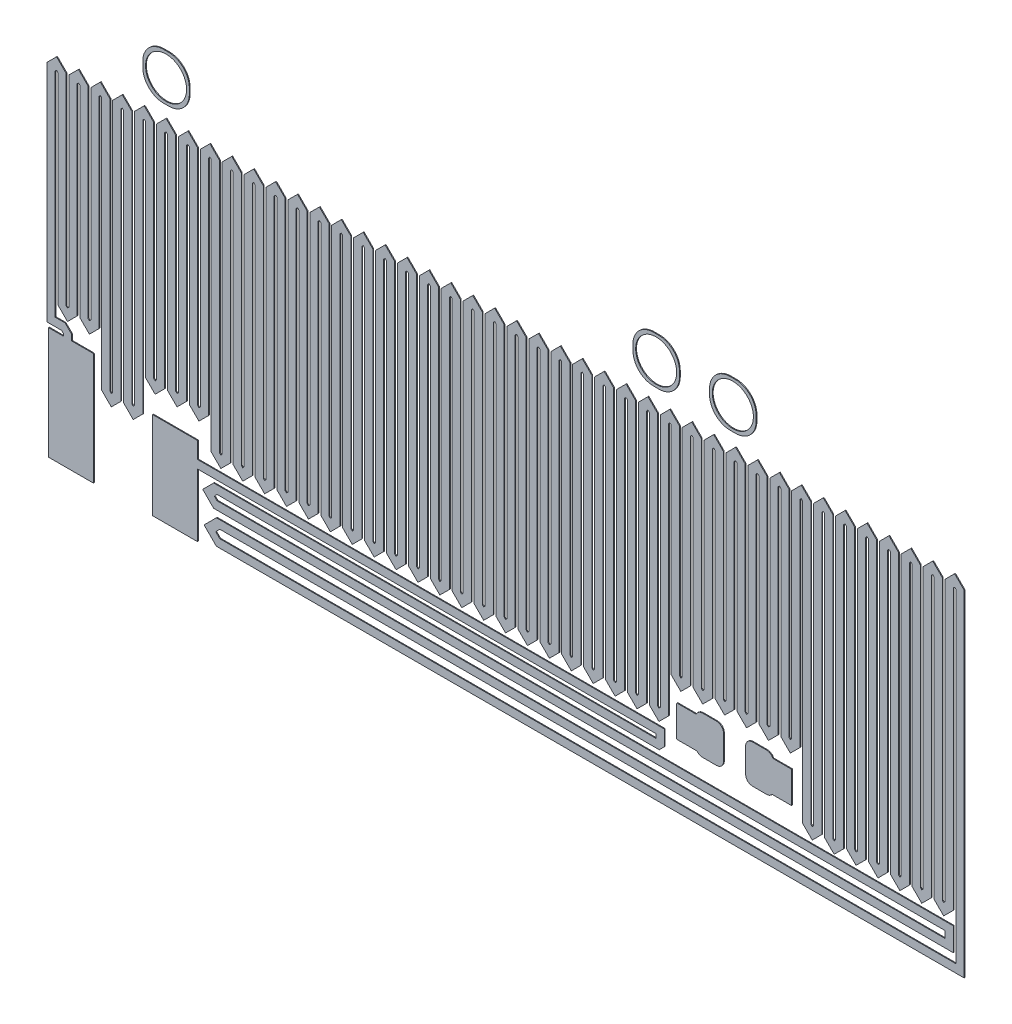
SolidWorks part; units mm, degrees
material "Pure Gold"
ref_plane "Front Plane" through (0, 0, 0) normal (0, 0, 1) x (1, 0, 0)
ref_plane "Top Plane" through (0, 0, 0) normal (0, 1, 0) x (1, 0, 0)
ref_plane "Right Plane" through (0, 0, 0) normal (1, 0, 0) x (0, 0, -1)
sketch "Sketch4" plane through (0, 0, 0) normal (0, 0, 1) x (1, 0, 0)
  line L0 (172.8, 114.607) -> (172.8, 114.657)
  line L1 (165.1587, 105.907) -> (165.211, 105.984)
  line L2 (165.211, 105.984) -> (165.292, 106.038)
  line L3 (165.292, 106.038) -> (165.387, 106.057)
  line L4 (165.387, 106.057) -> (165.912, 106.057)
  line L5 (165.912, 106.057) -> (166.008, 106.038)
  line L6 (166.008, 106.038) -> (166.089, 105.984)
  line L7 (166.089, 105.984) -> (166.143, 105.903)
  line L8 (166.143, 105.903) -> (166.162, 105.807)
  line L9 (166.162, 105.807) -> (166.162, 104.907)
  line L10 (166.162, 104.907) -> (166.143, 104.811)
  line L11 (166.143, 104.811) -> (166.089, 104.73)
  line L12 (166.089, 104.73) -> (166.008, 104.676)
  line L13 (166.008, 104.676) -> (165.912, 104.657)
  line L14 (165.912, 104.657) -> (165.387, 104.657)
  line L15 (165.387, 104.657) -> (165.292, 104.676)
  line L16 (165.292, 104.676) -> (165.211, 104.73)
  line L17 (165.211, 104.73) -> (165.1927, 104.757)
  line L18 (172, 114.607) -> (172, 114.657)
  line L19 (171.2, 114.607) -> (171.2, 114.657)
  line L20 (166.963, 105.807) -> (166.982, 105.903)
  line L21 (166.982, 105.903) -> (167.036, 105.984)
  line L22 (167.036, 105.984) -> (167.117, 106.038)
  line L23 (167.117, 106.038) -> (167.213, 106.057)
  line L24 (167.213, 106.057) -> (167.738, 106.057)
  line L25 (167.738, 106.057) -> (167.833, 106.038)
  line L26 (167.833, 106.038) -> (167.914, 105.984)
  line L27 (167.914, 105.984) -> (167.9663, 105.907)
  line L28 (170.4, 114.607) -> (170.4, 114.657)
  line L29 (169.6, 114.607) -> (169.6, 114.657)
  line L30 (168.8, 114.607) -> (168.8, 114.657)
  line L31 (167.9323, 104.757) -> (167.914, 104.73)
  line L32 (167.914, 104.73) -> (167.833, 104.676)
  line L33 (167.833, 104.676) -> (167.738, 104.657)
  line L34 (167.738, 104.657) -> (167.213, 104.657)
  line L35 (167.213, 104.657) -> (167.117, 104.676)
  line L36 (167.117, 104.676) -> (167.036, 104.73)
  line L37 (167.036, 104.73) -> (166.982, 104.811)
  line L38 (166.982, 104.811) -> (166.963, 104.907)
  line L39 (166.963, 104.907) -> (166.963, 105.807)
  line L40 (144.95, 115.507) -> (144.95, 117.207)
  line L41 (144.95, 117.207) -> (146.65, 117.207)
  line L42 (146.65, 117.207) -> (146.65, 115.507)
  line L43 (146.65, 115.507) -> (144.95, 115.507)
  line L44 (162.85, 115.507) -> (162.85, 117.207)
  line L45 (162.85, 117.207) -> (164.55, 117.207)
  line L46 (164.55, 117.207) -> (164.55, 115.507)
  line L47 (164.55, 115.507) -> (162.85, 115.507)
  line L48 (165.65, 115.507) -> (165.65, 117.207)
  line L49 (165.65, 117.207) -> (167.35, 117.207)
  line L50 (167.35, 117.207) -> (167.35, 115.507)
  line L51 (167.35, 115.507) -> (165.65, 115.507)
  line L52 (163.85, 104.357) -> (163.85, 104.707)
  line L53 (160.4, 114.657) -> (160.4, 105.407)
  line L54 (148.8, 114.657) -> (149, 114.857)
  line L55 (141.8, 114.807) -> (142, 114.607)
  line L56 (165.6, 106.757) -> (165.6, 114.607)
  line L57 (151.6, 114.657) -> (151.6, 105.407)
  line L58 (151.4, 114.857) -> (151.6, 114.657)
  line L59 (172, 104.457) -> (172, 114.607)
  line L60 (164, 104.857) -> (146.7, 104.857) construction
  line L61 (148.6, 105.207) -> (148.8, 105.407)
  line L62 (162.8, 114.657) -> (162.8, 105.407)
  line L63 (164, 105.407) -> (164, 114.607)
  line L64 (172.2, 114.857) -> (172.4, 114.657)
  line L65 (147.35, 104.007) -> (147.6, 104.257)
  line L66 (153.6, 105.407) -> (153.6, 114.607)
  line L67 (169.8, 114.857) -> (170, 114.657)
  line L68 (162, 105.407) -> (162.2, 105.207)
  line L69 (162.4, 114.657) -> (162.6, 114.857)
  line L70 (156.2, 114.857) -> (156.4, 114.657)
  line L71 (161, 114.857) -> (161.2, 114.657)
  line L72 (174.4, 114.657) -> (174.6, 114.857)
  line L73 (165.2, 114.657) -> (165.2, 106.757)
  line L74 (147.2, 114.657) -> (147.4, 114.857)
  line L75 (171.2, 104.457) -> (171.2, 114.607)
  line L76 (155.6, 114.657) -> (155.6, 105.407)
  line L77 (152, 105.407) -> (152, 114.607)
  line L78 (166, 106.807) -> (166.2, 106.607)
  line L79 (165.2, 106.757) -> (165.4, 106.557)
  line L80 (154, 105.407) -> (154.2, 105.207)
  line L81 (169.2, 104.457) -> (169.4, 104.257)
  line L82 (155, 105.207) -> (155.2, 105.407)
  line L83 (146, 114.657) -> (146, 106.557)
  line L84 (147.7, 103.207) -> (174.4, 103.207)
  line L85 (155.2, 114.657) -> (155.4, 114.857)
  line L86 (163.6, 114.657) -> (163.6, 105.407)
  line L87 (170.6, 114.857) -> (170.8, 114.657)
  line L88 (168.4, 106.807) -> (168.6, 106.607)
  line L89 (168.4, 114.657) -> (168.4, 106.807)
  line L90 (152, 114.657) -> (152.2, 114.857)
  line L91 (156, 105.407) -> (156, 114.607)
  line L92 (160.8, 114.657) -> (161, 114.857)
  line L93 (154.4, 114.657) -> (154.6, 114.857)
  line L94 (161.6, 114.657) -> (161.8, 114.857)
  line L95 (152.4, 114.657) -> (152.4, 105.407)
  line L96 (169.2, 114.657) -> (169.2, 104.457)
  line L97 (159.2, 114.657) -> (159.4, 114.857)
  line L98 (151.2, 114.657) -> (151.4, 114.857)
  line L99 (143.6, 114.607) -> (143.6, 105.357)
  line L100 (157.6, 114.657) -> (157.8, 114.857)
  line L101 (144, 114.607) -> (144.2, 114.807)
  line L102 (155.6, 105.407) -> (155.8, 105.207)
  line L103 (168.8, 106.807) -> (168.8, 114.607)
  line L104 (163, 105.207) -> (163.2, 105.407)
  line L105 (147, 106.307) -> (147.2, 106.507)
  line L106 (143.4, 114.807) -> (143.6, 114.607)
  line L107 (150.8, 114.657) -> (150.8, 105.407)
  line L108 (147.7, 102.607) -> (147.4, 102.907)
  line L109 (153.2, 105.407) -> (153.4, 105.207)
  line L110 (160.2, 114.857) -> (160.4, 114.657)
  line L111 (148.4, 105.407) -> (148.6, 105.207)
  line L112 (166.4, 106.807) -> (166.4, 114.607)
  line L113 (161.6, 105.407) -> (161.6, 114.607)
  line L114 (163.4, 114.857) -> (163.6, 114.657)
  line L115 (165, 114.857) -> (165.2, 114.657)
  line L116 (168, 114.657) -> (168.2, 114.857)
  line L117 (171.6, 114.657) -> (171.6, 104.457)
  line L118 (174.4, 103.757) -> (147.6, 103.757)
  line L119 (152.2, 114.857) -> (152.4, 114.657)
  line L120 (141.6, 114.607) -> (141.8, 114.807)
  line L121 (142, 114.607) -> (142, 107.257)
  line L122 (159.6, 114.657) -> (159.6, 105.407)
  line L123 (163.2, 114.657) -> (163.4, 114.857)
  line L124 (157.2, 105.407) -> (157.4, 105.207)
  line L125 (165.8, 114.857) -> (166, 114.657)
  line L126 (147.4, 102.907) -> (147.7, 103.207)
  line L127 (160.6, 105.207) -> (160.8, 105.407)
  line L128 (158.2, 105.207) -> (158.4, 105.407)
  line L129 (142.8, 107.257) -> (143, 107.057)
  line L130 (145.6, 114.657) -> (145.8, 114.857)
  line L131 (166.6, 114.857) -> (166.8, 114.657)
  line L132 (164.2, 114.857) -> (164.4, 114.657)
  line L133 (159.8, 105.207) -> (160, 105.407)
  line L134 (171.6, 104.457) -> (171.8, 104.257)
  line L135 (146.6, 114.857) -> (146.8, 114.657)
  line L136 (155.2, 105.407) -> (155.2, 114.607)
  line L137 (169.6, 114.657) -> (169.8, 114.857)
  line L138 (148.4, 114.657) -> (148.4, 105.407)
  line L139 (173, 114.857) -> (173.2, 114.657)
  line L140 (154.8, 105.407) -> (155, 105.207)
  line L141 (158.6, 114.857) -> (158.8, 114.657)
  line L142 (157.2, 114.657) -> (157.2, 105.407)
  line L143 (143.2, 114.607) -> (143.4, 114.807)
  line L144 (160, 105.407) -> (160, 114.607)
  line L145 (162.8, 105.407) -> (163, 105.207)
  line L146 (172, 114.657) -> (172.2, 114.857)
  line L147 (145.2, 106.557) -> (145.4, 106.357)
  line L148 (147.6, 104.257) -> (163.75, 104.257)
  line L149 (173.2, 114.657) -> (173.2, 104.457)
  line L150 (158.8, 114.657) -> (158.8, 105.407)
  line L151 (174, 104.457) -> (174.2, 104.257)
  line L152 (145, 114.857) -> (145.2, 114.657)
  line L153 (143.8, 105.157) -> (144, 105.357)
  line L154 (161.4, 105.207) -> (161.6, 105.407)
  line L155 (146, 106.557) -> (146.2, 106.357)
  line L156 (154.4, 105.407) -> (154.4, 114.607)
  line L157 (163.2, 105.407) -> (163.2, 114.607)
  line L158 (172.4, 114.657) -> (172.4, 104.457)
  line L159 (149, 114.857) -> (149.2, 114.657)
  line L160 (157.6, 105.407) -> (157.6, 114.607)
  line L161 (149.8, 114.857) -> (150, 114.657)
  line L162 (164.4, 106.757) -> (164.6, 106.557)
  line L163 (170, 114.657) -> (170, 104.407)
  line L164 (157, 114.857) -> (157.2, 114.657)
  line L165 (161.2, 105.407) -> (161.4, 105.207)
  line L166 (168.2, 114.857) -> (168.4, 114.657)
  line L167 (154.6, 114.857) -> (154.8, 114.657)
  line L168 (163.6, 105.407) -> (163.8, 105.207)
  line L169 (173.2, 104.457) -> (173.4, 104.257)
  line L170 (164.8, 106.757) -> (164.8, 114.607)
  line L171 (163.85, 104.707) -> (146.7, 104.707) construction
  line L172 (145.8, 114.857) -> (146, 114.657)
  line L173 (159.6, 105.407) -> (159.8, 105.207)
  line L174 (156.6, 105.207) -> (156.8, 105.407)
  line L175 (170.8, 114.657) -> (170.8, 104.457)
  line L176 (168.6, 106.607) -> (168.8, 106.807)
  line L177 (150.8, 105.407) -> (151, 105.207)
  line L178 (156.8, 105.407) -> (156.8, 114.607)
  line L179 (151.8, 105.207) -> (152, 105.407)
  line L180 (166, 114.657) -> (166, 106.807)
  line L181 (163.8, 105.207) -> (164, 105.407)
  line L182 (152.8, 105.407) -> (152.8, 114.607)
  line L183 (168.8, 114.657) -> (169, 114.857)
  line L184 (167.4, 114.857) -> (167.6, 114.657)
  line L185 (159.2, 105.407) -> (159.2, 114.607)
  line L186 (153, 114.857) -> (153.2, 114.657)
  line L187 (162.6, 114.857) -> (162.8, 114.657)
  line L188 (142.4, 114.607) -> (142.6, 114.807)
  line L189 (167.2, 106.807) -> (167.2, 114.607)
  line L190 (145.2, 114.657) -> (145.2, 106.557)
  line L191 (146.8, 114.657) -> (146.8, 106.507)
  line L192 (143.6, 105.357) -> (143.8, 105.157)
  line L193 (144.4, 105.357) -> (144.6, 105.157)
  line L194 (158, 114.657) -> (158, 105.407)
  line L195 (149.2, 105.407) -> (149.4, 105.207)
  line L196 (161.8, 114.857) -> (162, 114.657)
  line L197 (167.2, 114.657) -> (167.4, 114.857)
  line L198 (154.8, 114.657) -> (154.8, 105.407)
  line L199 (150, 114.657) -> (150, 105.407)
  line L200 (147.4, 114.857) -> (147.6, 114.657)
  line L201 (150.4, 105.407) -> (150.4, 114.607)
  line L202 (142.6, 114.807) -> (142.8, 114.607)
  line L203 (147.6, 105.407) -> (147.8, 105.207)
  line L204 (151, 105.207) -> (151.2, 105.407)
  line L205 (173.8, 114.857) -> (174, 114.657)
  line L206 (149.4, 105.207) -> (149.6, 105.407)
  line L207 (170, 104.407) -> (170.2, 104.207)
  line L208 (165.6, 114.657) -> (165.8, 114.857)
  line L209 (168, 106.807) -> (168, 114.607)
  line L210 (149.6, 114.657) -> (149.8, 114.857)
  line L211 (146.8, 106.507) -> (147, 106.307)
  line L212 (174.4, 104.457) -> (174.4, 114.657)
  line L213 (167.6, 106.807) -> (167.8, 106.607)
  line L214 (156.4, 105.407) -> (156.6, 105.207)
  line L215 (158.4, 105.407) -> (158.4, 114.607)
  line L216 (162.2, 105.207) -> (162.4, 105.407)
  line L217 (146.4, 106.557) -> (146.4, 114.607)
  line L218 (161.2, 114.657) -> (161.2, 105.407)
  line L219 (153.4, 105.207) -> (153.6, 105.407)
  line L220 (149.6, 105.407) -> (149.6, 114.607)
  line L221 (151.6, 105.407) -> (151.8, 105.207)
  line L222 (144.8, 105.407) -> (144.8, 114.607)
  line L223 (174.6, 114.857) -> (174.8, 114.657)
  line L224 (170.4, 104.407) -> (170.4, 114.607)
  line L225 (167.6, 114.657) -> (167.6, 106.807)
  line L226 (172.8, 114.657) -> (173, 114.857)
  line L227 (152.6, 105.207) -> (152.8, 105.407)
  line L228 (166.8, 114.657) -> (166.8, 106.807)
  line L229 (174.2, 104.257) -> (174.4, 104.457)
  line L230 (151.2, 105.407) -> (151.2, 114.607)
  line L231 (169.4, 104.257) -> (169.6, 104.457)
  line L232 (153.8, 114.857) -> (154, 114.657)
  line L233 (165.4, 106.557) -> (165.6, 106.757)
  line L234 (142.2, 107.057) -> (142.4, 107.257)
  line L235 (155.8, 105.207) -> (156, 105.407)
  line L236 (166.2, 106.607) -> (166.4, 106.807)
  line L237 (160.4, 105.407) -> (160.6, 105.207)
  line L238 (163.75, 104.257) -> (163.85, 104.357)
  line L239 (166.4, 114.657) -> (166.6, 114.857)
  line L240 (142.8, 114.607) -> (142.8, 107.257)
  line L241 (174.4, 103.207) -> (174.4, 103.757)
  line L242 (154.2, 105.207) -> (154.4, 105.407)
  line L243 (148.8, 105.407) -> (148.8, 114.607)
  line L244 (171.8, 104.257) -> (172, 104.457)
  line L245 (170.4, 114.657) -> (170.6, 114.857)
  line L246 (157.8, 114.857) -> (158, 114.657)
  line L247 (150.2, 105.207) -> (150.4, 105.407)
  line L248 (160, 114.657) -> (160.2, 114.857)
  line L249 (144, 105.357) -> (144, 114.557)
  line L250 (170.2, 104.207) -> (170.4, 104.407)
  line L251 (153.2, 114.657) -> (153.2, 105.407)
  line L252 (144.8, 114.657) -> (145, 114.857)
  line L253 (152.4, 105.407) -> (152.6, 105.207)
  line L254 (169, 114.857) -> (169.2, 114.657)
  line L255 (143, 107.057) -> (143.2, 107.257)
  line L256 (159, 105.207) -> (159.2, 105.407)
  line L257 (173.6, 114.657) -> (173.8, 114.857)
  line L258 (144.4, 114.607) -> (144.4, 105.357)
  line L259 (142.35, 106.307) -> (143.136, 106.307)
  line L260 (162, 114.657) -> (162, 105.407)
  line L261 (149.2, 114.657) -> (149.2, 105.407)
  line L262 (158, 105.407) -> (158.2, 105.207)
  line L263 (144.6, 105.157) -> (144.8, 105.357)
  line L264 (146.4, 114.657) -> (146.6, 114.857)
  line L265 (144.2, 114.807) -> (144.4, 114.607)
  line L266 (170.8, 104.457) -> (171, 104.257)
  line L267 (173.4, 104.257) -> (173.6, 104.457)
  line L268 (172.6, 104.257) -> (172.8, 104.457)
  line L269 (148.2, 114.857) -> (148.4, 114.657)
  line L270 (169.6, 104.457) -> (169.6, 114.607)
  line L271 (157.4, 105.207) -> (157.6, 105.407)
  line L272 (154, 114.657) -> (154, 105.407)
  line L273 (171, 104.257) -> (171.2, 104.457)
  line L274 (143.2, 107.257) -> (143.2, 114.557)
  line L275 (171.4, 114.857) -> (171.6, 114.657)
  line L276 (173.6, 104.457) -> (173.6, 114.657)
  line L277 (147.6, 103.757) -> (147.35, 104.007)
  line L278 (153.6, 114.657) -> (153.8, 114.857)
  line L279 (174.8, 102.607) -> (147.7, 102.607)
  line L280 (172.8, 104.457) -> (172.8, 114.607)
  line L281 (148, 105.407) -> (148, 114.607)
  line L282 (147.8, 105.207) -> (148, 105.407)
  line L283 (156, 114.657) -> (156.2, 114.857)
  line L284 (162.4, 105.407) -> (162.4, 114.607)
  line L285 (156.8, 114.657) -> (157, 114.857)
  line L286 (164.8, 114.657) -> (165, 114.857)
  line L287 (159.4, 114.857) -> (159.6, 114.657)
  line L288 (167, 106.607) -> (167.2, 106.807)
  line L289 (160.8, 105.407) -> (160.8, 114.607)
  line L290 (142.4, 107.257) -> (142.4, 114.557)
  line L291 (174, 114.657) -> (174, 104.457)
  line L292 (152.8, 114.657) -> (153, 114.857)
  line L293 (164, 114.657) -> (164.2, 114.857)
  line L294 (158.4, 114.657) -> (158.6, 114.857)
  line L295 (174.8, 114.657) -> (174.8, 102.607)
  line L296 (164.4, 114.657) -> (164.4, 106.757)
  line L297 (147.2, 106.507) -> (147.2, 114.607)
  line L298 (166.8, 106.807) -> (167, 106.607)
  line L299 (155.4, 114.857) -> (155.6, 114.657)
  line L300 (156.4, 114.657) -> (156.4, 105.407)
  line L301 (172.4, 104.457) -> (172.6, 104.257)
  line L302 (145.6, 106.557) -> (145.6, 114.607)
  line L303 (171.2, 114.657) -> (171.4, 114.857)
  line L304 (167.8, 106.607) -> (168, 106.807)
  line L305 (146.2, 106.357) -> (146.4, 106.557)
  line L306 (163.7, 104.557) -> (146.7, 104.557) construction
  line L307 (146.95, 104.557) -> (146.95, 102.271)
  line L308 (150.6, 114.857) -> (150.8, 114.657)
  line L309 (150, 105.407) -> (150.2, 105.207)
  line L310 (158.8, 105.407) -> (159, 105.207)
  line L311 (142, 107.257) -> (142.2, 107.057)
  line L312 (150.4, 114.657) -> (150.6, 114.857)
  line L313 (148, 114.657) -> (148.2, 114.857)
  line L314 (147.6, 114.657) -> (147.6, 105.407)
  line L315 (145.4, 106.357) -> (145.6, 106.557)
  line L316 (164.6, 106.557) -> (164.8, 106.757)
  line L317 (168, 114.607) -> (168, 114.657)
  line L318 (167.2, 114.607) -> (167.2, 114.657)
  line L319 (166.4, 114.607) -> (166.4, 114.657)
  line L320 (165.6, 114.607) -> (165.6, 114.657)
  line L321 (165.1927, 104.757) -> (164.464, 104.757)
  line L322 (164.464, 104.757) -> (164.454, 104.761)
  line L323 (164.454, 104.761) -> (164.45, 104.771)
  line L324 (164.45, 104.771) -> (164.45, 105.893)
  line L325 (164.45, 105.893) -> (164.454, 105.903)
  line L326 (164.454, 105.903) -> (164.464, 105.907)
  line L327 (164.464, 105.907) -> (165.1587, 105.907)
  line L328 (164.8, 114.607) -> (164.8, 114.657)
  line L329 (143.146, 106.303) -> (143.15, 106.293)
  line L330 (143.15, 106.293) -> (143.15, 102.222)
  line L331 (143.15, 102.222) -> (143.146, 102.212)
  line L332 (143.146, 102.212) -> (143.136, 102.208)
  line L333 (143.136, 102.208) -> (141.514, 102.208)
  line L334 (141.514, 102.208) -> (141.504, 102.212)
  line L335 (141.504, 102.212) -> (141.5, 102.222)
  line L336 (141.5, 102.222) -> (141.5, 106.293)
  line L337 (141.5, 106.293) -> (141.504, 106.303)
  line L338 (141.504, 106.303) -> (141.514, 106.307)
  line L339 (141.514, 106.307) -> (142.05, 106.307)
  line L340 (143.136, 106.307) -> (143.146, 106.303)
  line L341 (168.646, 105.903) -> (168.65, 105.893)
  line L342 (168.65, 105.893) -> (168.65, 104.771)
  line L343 (168.65, 104.771) -> (168.646, 104.761)
  line L344 (168.646, 104.761) -> (168.636, 104.757)
  line L345 (168.636, 104.757) -> (167.9323, 104.757)
  line L346 (164, 114.607) -> (164, 114.657)
  line L347 (163.2, 114.607) -> (163.2, 114.657)
  line L348 (162.4, 114.607) -> (162.4, 114.657)
  line L349 (161.6, 114.607) -> (161.6, 114.657)
  line L350 (160.8, 114.607) -> (160.8, 114.657)
  line L351 (167.9663, 105.907) -> (168.636, 105.907)
  line L352 (168.636, 105.907) -> (168.646, 105.903)
  line L353 (146.946, 105.453) -> (146.95, 105.443)
  line L354 (146.95, 105.443) -> (146.95, 104.857)
  line L355 (146.95, 102.271) -> (146.946, 102.261)
  line L356 (146.946, 102.261) -> (146.936, 102.257)
  line L357 (146.936, 102.257) -> (145.314, 102.257)
  line L358 (145.314, 102.257) -> (145.304, 102.261)
  line L359 (145.304, 102.261) -> (145.3, 102.271)
  line L360 (145.3, 102.271) -> (145.3, 105.443)
  line L361 (145.3, 105.443) -> (145.304, 105.453)
  line L362 (145.304, 105.453) -> (145.314, 105.457)
  line L363 (145.314, 105.457) -> (146.936, 105.457)
  line L364 (146.936, 105.457) -> (146.946, 105.453)
  line L365 (151.835, 117.707) -> (151.835, 115.608)
  line L366 (147.749, 115.608) -> (147.749, 117.707)
  line L367 (155.567, 115.608) -> (155.567, 117.707)
  line L368 (175.558, 102.207) -> (175.558, 117.707)
  line L369 (140.558, 117.707) -> (140.558, 102.207)
  line L370 (147.749, 117.707) -> (140.558, 117.707)
  line L371 (151.835, 115.608) -> (147.749, 115.608)
  line L372 (161.898, 117.707) -> (161.898, 115.608)
  line L373 (155.567, 117.707) -> (151.835, 117.707)
  line L374 (161.898, 115.608) -> (155.567, 115.608)
  line L375 (140.558, 102.207) -> (175.558, 102.207)
  line L376 (175.558, 117.707) -> (161.898, 117.707)
  line L377 (160, 114.607) -> (160, 114.657)
  line L378 (159.2, 114.607) -> (159.2, 114.657)
  line L379 (158.4, 114.607) -> (158.4, 114.657)
  line L380 (157.6, 114.607) -> (157.6, 114.657)
  line L381 (156.8, 114.607) -> (156.8, 114.657)
  line L382 (156, 114.607) -> (156, 114.657)
  line L383 (155.2, 114.607) -> (155.2, 114.657)
  line L384 (154.4, 114.607) -> (154.4, 114.657)
  line L385 (153.6, 114.607) -> (153.6, 114.657)
  line L386 (152.8, 114.607) -> (152.8, 114.657)
  line L387 (152, 114.607) -> (152, 114.657)
  line L388 (151.2, 114.607) -> (151.2, 114.657)
  line L389 (150.4, 114.607) -> (150.4, 114.657)
  line L390 (149.6, 114.607) -> (149.6, 114.657)
  line L391 (148.8, 114.607) -> (148.8, 114.657)
  line L392 (148, 114.607) -> (148, 114.657)
  line L393 (147.2, 114.607) -> (147.2, 114.657)
  line L394 (146.4, 114.607) -> (146.4, 114.657)
  line L395 (145.6, 114.607) -> (145.6, 114.657)
  line L396 (144.8, 114.607) -> (144.8, 114.657)
  line L397 (144, 114.557) -> (144, 114.607)
  line L398 (143.2, 114.557) -> (143.2, 114.607)
  line L399 (142.4, 114.557) -> (142.4, 114.607)
  line L400 (144.8, 105.357) -> (144.8, 105.407)
  line L401 (142.35, 106.307) -> (142.35, 106.5191)
  line L402 (142.35, 106.5191) -> (142.1121, 106.757)
  line L403 (142.1121, 106.757) -> (141.75, 106.757)
  line L404 (141.75, 106.757) -> (141.75, 114.5449)
  line L405 (141.75, 114.5449) -> (141.8, 114.5949)
  line L406 (141.8, 114.5949) -> (141.85, 114.5449)
  line L407 (141.85, 114.5449) -> (141.85, 107.1949)
  line L408 (141.85, 107.1949) -> (142.2, 106.8449)
  line L409 (142.2, 106.8449) -> (142.55, 107.1949)
  line L410 (142.55, 107.1949) -> (142.55, 114.5449)
  line L411 (142.55, 114.5449) -> (142.55, 114.5449)
  line L412 (142.55, 114.5449) -> (142.6, 114.5949)
  line L413 (142.6, 114.5949) -> (142.65, 114.5449)
  line L414 (142.65, 114.5449) -> (142.65, 107.1949)
  line L415 (142.65, 107.1949) -> (143, 106.8449)
  line L416 (143, 106.8449) -> (143.35, 107.1949)
  line L417 (143.35, 107.1949) -> (143.35, 114.5449)
  line L418 (143.35, 114.5449) -> (143.35, 114.5449)
  line L419 (143.35, 114.5449) -> (143.4, 114.5949)
  line L420 (143.4, 114.5949) -> (143.45, 114.5449)
  line L421 (143.45, 114.5449) -> (143.45, 105.2949)
  line L422 (143.45, 105.2949) -> (143.8, 104.9449)
  line L423 (143.8, 104.9449) -> (144.15, 105.2949)
  line L424 (144.15, 105.2949) -> (144.15, 114.5449)
  line L425 (144.15, 114.5449) -> (144.15, 114.5449)
  line L426 (144.15, 114.5449) -> (144.2, 114.5949)
  line L427 (144.2, 114.5949) -> (144.25, 114.5449)
  line L428 (144.25, 114.5449) -> (144.25, 105.2949)
  line L429 (144.25, 105.2949) -> (144.6, 104.9449)
  line L430 (144.6, 104.9449) -> (144.95, 105.2949)
  line L431 (144.95, 105.2949) -> (144.95, 105.407)
  line L432 (144.95, 105.407) -> (144.95, 114.5949)
  line L433 (144.95, 114.5949) -> (144.95, 114.5949)
  line L434 (144.95, 114.5949) -> (145, 114.6449)
  line L435 (145, 114.6449) -> (145.05, 114.5949)
  line L436 (145.05, 114.5949) -> (145.05, 106.4949)
  line L437 (145.05, 106.4949) -> (145.4, 106.1449)
  line L438 (145.4, 106.1449) -> (145.75, 106.4949)
  line L439 (145.75, 106.4949) -> (145.75, 114.5949)
  line L440 (145.75, 114.5949) -> (145.75, 114.5949)
  line L441 (145.75, 114.5949) -> (145.8, 114.6449)
  line L442 (145.8, 114.6449) -> (145.85, 114.5949)
  line L443 (145.85, 114.5949) -> (145.85, 106.4949)
  line L444 (145.85, 106.4949) -> (146.2, 106.1449)
  line L445 (146.2, 106.1449) -> (146.55, 106.4949)
  line L446 (146.55, 106.4949) -> (146.55, 114.5949)
  line L447 (146.55, 114.5949) -> (146.55, 114.5949)
  line L448 (146.55, 114.5949) -> (146.6, 114.6449)
  line L449 (146.6, 114.6449) -> (146.65, 114.5949)
  line L450 (146.65, 114.5949) -> (146.65, 106.4449)
  line L451 (146.65, 106.4449) -> (147, 106.0949)
  line L452 (147, 106.0949) -> (147.35, 106.4449)
  line L453 (147.35, 106.4449) -> (147.35, 114.5949)
  line L454 (147.35, 114.5949) -> (147.35, 114.5949)
  line L455 (147.35, 114.5949) -> (147.4, 114.6449)
  line L456 (147.4, 114.6449) -> (147.45, 114.5949)
  line L457 (147.45, 114.5949) -> (147.45, 105.3449)
  line L458 (147.45, 105.3449) -> (147.8, 104.9949)
  line L459 (147.8, 104.9949) -> (148.15, 105.3449)
  line L460 (148.15, 105.3449) -> (148.15, 114.5949)
  line L461 (148.15, 114.5949) -> (148.15, 114.5949)
  line L462 (148.15, 114.5949) -> (148.2, 114.6449)
  line L463 (148.2, 114.6449) -> (148.25, 114.5949)
  line L464 (148.25, 114.5949) -> (148.25, 105.3449)
  line L465 (148.25, 105.3449) -> (148.6, 104.9949)
  line L466 (148.6, 104.9949) -> (148.95, 105.3449)
  line L467 (148.95, 105.3449) -> (148.95, 114.5949)
  line L468 (148.95, 114.5949) -> (148.95, 114.5949)
  line L469 (148.95, 114.5949) -> (149, 114.6449)
  line L470 (149, 114.6449) -> (149.05, 114.5949)
  line L471 (149.05, 114.5949) -> (149.05, 105.3449)
  line L472 (149.05, 105.3449) -> (149.4, 104.9949)
  line L473 (149.4, 104.9949) -> (149.75, 105.3449)
  line L474 (149.75, 105.3449) -> (149.75, 114.5949)
  line L475 (149.75, 114.5949) -> (149.75, 114.5949)
  line L476 (149.75, 114.5949) -> (149.8, 114.6449)
  line L477 (149.8, 114.6449) -> (149.85, 114.5949)
  line L478 (149.85, 114.5949) -> (149.85, 105.3449)
  line L479 (149.85, 105.3449) -> (150.2, 104.9949)
  line L480 (150.2, 104.9949) -> (150.55, 105.3449)
  line L481 (150.55, 105.3449) -> (150.55, 114.5949)
  line L482 (150.55, 114.5949) -> (150.55, 114.5949)
  line L483 (150.55, 114.5949) -> (150.6, 114.6449)
  line L484 (150.6, 114.6449) -> (150.65, 114.5949)
  line L485 (150.65, 114.5949) -> (150.65, 105.3449)
  line L486 (150.65, 105.3449) -> (151, 104.9949)
  line L487 (151, 104.9949) -> (151.35, 105.3449)
  line L488 (151.35, 105.3449) -> (151.35, 114.5949)
  line L489 (151.35, 114.5949) -> (151.35, 114.5949)
  line L490 (151.35, 114.5949) -> (151.4, 114.6449)
  line L491 (151.4, 114.6449) -> (151.45, 114.5949)
  line L492 (151.45, 114.5949) -> (151.45, 105.3449)
  line L493 (151.45, 105.3449) -> (151.8, 104.9949)
  line L494 (151.8, 104.9949) -> (152.15, 105.3449)
  line L495 (152.15, 105.3449) -> (152.15, 114.5949)
  line L496 (152.15, 114.5949) -> (152.15, 114.5949)
  line L497 (152.15, 114.5949) -> (152.2, 114.6449)
  line L498 (152.2, 114.6449) -> (152.25, 114.5949)
  line L499 (152.25, 114.5949) -> (152.25, 105.3449)
  line L500 (152.25, 105.3449) -> (152.6, 104.9949)
  line L501 (152.6, 104.9949) -> (152.95, 105.3449)
  line L502 (152.95, 105.3449) -> (152.95, 114.5949)
  line L503 (152.95, 114.5949) -> (152.95, 114.5949)
  line L504 (152.95, 114.5949) -> (153, 114.6449)
  line L505 (153, 114.6449) -> (153.05, 114.5949)
  line L506 (153.05, 114.5949) -> (153.05, 105.3449)
  line L507 (153.05, 105.3449) -> (153.4, 104.9949)
  line L508 (153.4, 104.9949) -> (153.75, 105.3449)
  line L509 (153.75, 105.3449) -> (153.75, 114.5949)
  line L510 (153.75, 114.5949) -> (153.75, 114.5949)
  line L511 (153.75, 114.5949) -> (153.8, 114.6449)
  line L512 (153.8, 114.6449) -> (153.85, 114.5949)
  line L513 (153.85, 114.5949) -> (153.85, 105.3449)
  line L514 (153.85, 105.3449) -> (154.2, 104.9949)
  line L515 (154.2, 104.9949) -> (154.55, 105.3449)
  line L516 (154.55, 105.3449) -> (154.55, 114.5949)
  line L517 (154.55, 114.5949) -> (154.55, 114.5949)
  line L518 (154.55, 114.5949) -> (154.6, 114.6449)
  line L519 (154.6, 114.6449) -> (154.65, 114.5949)
  line L520 (154.65, 114.5949) -> (154.65, 105.3449)
  line L521 (154.65, 105.3449) -> (155, 104.9949)
  line L522 (155, 104.9949) -> (155.35, 105.3449)
  line L523 (155.35, 105.3449) -> (155.35, 114.5949)
  line L524 (155.35, 114.5949) -> (155.35, 114.5949)
  line L525 (155.35, 114.5949) -> (155.4, 114.6449)
  line L526 (155.4, 114.6449) -> (155.45, 114.5949)
  line L527 (155.45, 114.5949) -> (155.45, 105.3449)
  line L528 (155.45, 105.3449) -> (155.8, 104.9949)
  line L529 (155.8, 104.9949) -> (156.15, 105.3449)
  line L530 (156.15, 105.3449) -> (156.15, 114.5949)
  line L531 (156.15, 114.5949) -> (156.15, 114.5949)
  line L532 (156.15, 114.5949) -> (156.2, 114.6449)
  line L533 (156.2, 114.6449) -> (156.25, 114.5949)
  line L534 (156.25, 114.5949) -> (156.25, 105.3449)
  line L535 (156.25, 105.3449) -> (156.6, 104.9949)
  line L536 (156.6, 104.9949) -> (156.95, 105.3449)
  line L537 (156.95, 105.3449) -> (156.95, 114.5949)
  line L538 (156.95, 114.5949) -> (156.95, 114.5949)
  line L539 (156.95, 114.5949) -> (157, 114.6449)
  line L540 (157, 114.6449) -> (157.05, 114.5949)
  line L541 (157.05, 114.5949) -> (157.05, 105.3449)
  line L542 (157.05, 105.3449) -> (157.4, 104.9949)
  line L543 (157.4, 104.9949) -> (157.75, 105.3449)
  line L544 (157.75, 105.3449) -> (157.75, 114.5949)
  line L545 (157.75, 114.5949) -> (157.75, 114.5949)
  line L546 (157.75, 114.5949) -> (157.8, 114.6449)
  line L547 (157.8, 114.6449) -> (157.85, 114.5949)
  line L548 (157.85, 114.5949) -> (157.85, 105.3449)
  line L549 (157.85, 105.3449) -> (158.2, 104.9949)
  line L550 (158.2, 104.9949) -> (158.55, 105.3449)
  line L551 (158.55, 105.3449) -> (158.55, 114.5949)
  line L552 (158.55, 114.5949) -> (158.55, 114.5949)
  line L553 (158.55, 114.5949) -> (158.6, 114.6449)
  line L554 (158.6, 114.6449) -> (158.65, 114.5949)
  line L555 (158.65, 114.5949) -> (158.65, 105.3449)
  line L556 (158.65, 105.3449) -> (159, 104.9949)
  line L557 (159, 104.9949) -> (159.35, 105.3449)
  line L558 (159.35, 105.3449) -> (159.35, 114.5949)
  line L559 (159.35, 114.5949) -> (159.35, 114.5949)
  line L560 (159.35, 114.5949) -> (159.4, 114.6449)
  line L561 (159.4, 114.6449) -> (159.45, 114.5949)
  line L562 (159.45, 114.5949) -> (159.45, 105.3449)
  line L563 (159.45, 105.3449) -> (159.8, 104.9949)
  line L564 (159.8, 104.9949) -> (160.15, 105.3449)
  line L565 (160.15, 105.3449) -> (160.15, 114.5949)
  line L566 (160.15, 114.5949) -> (160.15, 114.5949)
  line L567 (160.15, 114.5949) -> (160.2, 114.6449)
  line L568 (160.2, 114.6449) -> (160.25, 114.5949)
  line L569 (160.25, 114.5949) -> (160.25, 105.3449)
  line L570 (160.25, 105.3449) -> (160.6, 104.9949)
  line L571 (160.6, 104.9949) -> (160.95, 105.3449)
  line L572 (160.95, 105.3449) -> (160.95, 114.5949)
  line L573 (160.95, 114.5949) -> (160.95, 114.5949)
  line L574 (160.95, 114.5949) -> (161, 114.6449)
  line L575 (161, 114.6449) -> (161.05, 114.5949)
  line L576 (161.05, 114.5949) -> (161.05, 105.3449)
  line L577 (161.05, 105.3449) -> (161.4, 104.9949)
  line L578 (161.4, 104.9949) -> (161.75, 105.3449)
  line L579 (161.75, 105.3449) -> (161.75, 114.5949)
  line L580 (161.75, 114.5949) -> (161.75, 114.5949)
  line L581 (161.75, 114.5949) -> (161.8, 114.6449)
  line L582 (161.8, 114.6449) -> (161.85, 114.5949)
  line L583 (161.85, 114.5949) -> (161.85, 105.3449)
  line L584 (161.85, 105.3449) -> (162.2, 104.9949)
  line L585 (162.2, 104.9949) -> (162.55, 105.3449)
  line L586 (162.55, 105.3449) -> (162.55, 114.5949)
  line L587 (162.55, 114.5949) -> (162.55, 114.5949)
  line L588 (162.55, 114.5949) -> (162.6, 114.6449)
  line L589 (162.6, 114.6449) -> (162.65, 114.5949)
  line L590 (162.65, 114.5949) -> (162.65, 105.3449)
  line L591 (162.65, 105.3449) -> (163, 104.9949)
  line L592 (163, 104.9949) -> (163.35, 105.3449)
  line L593 (163.35, 105.3449) -> (163.35, 114.5949)
  line L594 (163.35, 114.5949) -> (163.35, 114.5949)
  line L595 (163.35, 114.5949) -> (163.4, 114.6449)
  line L596 (163.4, 114.6449) -> (163.45, 114.5949)
  line L597 (163.45, 114.5949) -> (163.45, 105.3449)
  line L598 (163.45, 105.3449) -> (163.8, 104.9949)
  line L599 (163.8, 104.9949) -> (164.15, 105.3449)
  line L600 (164.15, 105.3449) -> (164.15, 114.5949)
  line L601 (164.15, 114.5949) -> (164.15, 114.5949)
  line L602 (164.15, 114.5949) -> (164.2, 114.6449)
  line L603 (164.2, 114.6449) -> (164.25, 114.5949)
  line L604 (164.25, 114.5949) -> (164.25, 106.6949)
  line L605 (164.25, 106.6949) -> (164.6, 106.3449)
  line L606 (164.6, 106.3449) -> (164.95, 106.6949)
  line L607 (164.95, 106.6949) -> (164.95, 114.5949)
  line L608 (164.95, 114.5949) -> (164.95, 114.5949)
  line L609 (164.95, 114.5949) -> (165, 114.6449)
  line L610 (165, 114.6449) -> (165.05, 114.5949)
  line L611 (165.05, 114.5949) -> (165.05, 106.6949)
  line L612 (165.05, 106.6949) -> (165.4, 106.3449)
  line L613 (165.4, 106.3449) -> (165.75, 106.6949)
  line L614 (165.75, 106.6949) -> (165.75, 114.5949)
  line L615 (165.75, 114.5949) -> (165.75, 114.5949)
  line L616 (165.75, 114.5949) -> (165.8, 114.6449)
  line L617 (165.8, 114.6449) -> (165.85, 114.5949)
  line L618 (165.85, 114.5949) -> (165.85, 106.7449)
  line L619 (165.85, 106.7449) -> (166.2, 106.3949)
  line L620 (166.2, 106.3949) -> (166.55, 106.7449)
  line L621 (166.55, 106.7449) -> (166.55, 114.5949)
  line L622 (166.55, 114.5949) -> (166.55, 114.5949)
  line L623 (166.55, 114.5949) -> (166.6, 114.6449)
  line L624 (166.6, 114.6449) -> (166.65, 114.5949)
  line L625 (166.65, 114.5949) -> (166.65, 106.7449)
  line L626 (166.65, 106.7449) -> (167, 106.3949)
  line L627 (167, 106.3949) -> (167.35, 106.7449)
  line L628 (167.35, 106.7449) -> (167.35, 114.5949)
  line L629 (167.35, 114.5949) -> (167.35, 114.5949)
  line L630 (167.35, 114.5949) -> (167.4, 114.6449)
  line L631 (167.4, 114.6449) -> (167.45, 114.5949)
  line L632 (167.45, 114.5949) -> (167.45, 106.7449)
  line L633 (167.45, 106.7449) -> (167.8, 106.3949)
  line L634 (167.8, 106.3949) -> (168.15, 106.7449)
  line L635 (168.15, 106.7449) -> (168.15, 114.5949)
  line L636 (168.15, 114.5949) -> (168.15, 114.5949)
  line L637 (168.15, 114.5949) -> (168.2, 114.6449)
  line L638 (168.2, 114.6449) -> (168.25, 114.5949)
  line L639 (168.25, 114.5949) -> (168.25, 106.7449)
  line L640 (168.25, 106.7449) -> (168.6, 106.3949)
  line L641 (168.6, 106.3949) -> (168.95, 106.7449)
  line L642 (168.95, 106.7449) -> (168.95, 114.5949)
  line L643 (168.95, 114.5949) -> (168.95, 114.5949)
  line L644 (168.95, 114.5949) -> (169, 114.6449)
  line L645 (169, 114.6449) -> (169.05, 114.5949)
  line L646 (169.05, 114.5949) -> (169.05, 104.3949)
  line L647 (169.05, 104.3949) -> (169.4, 104.0449)
  line L648 (169.4, 104.0449) -> (169.75, 104.3949)
  line L649 (169.75, 104.3949) -> (169.75, 114.5949)
  line L650 (169.75, 114.5949) -> (169.75, 114.5949)
  line L651 (169.75, 114.5949) -> (169.8, 114.6449)
  line L652 (169.8, 114.6449) -> (169.85, 114.5949)
  line L653 (169.85, 114.5949) -> (169.85, 104.3449)
  line L654 (169.85, 104.3449) -> (170.2, 103.9949)
  line L655 (170.2, 103.9949) -> (170.55, 104.3449)
  line L656 (170.55, 104.3449) -> (170.55, 114.5949)
  line L657 (170.55, 114.5949) -> (170.55, 114.5949)
  line L658 (170.55, 114.5949) -> (170.6, 114.6449)
  line L659 (170.6, 114.6449) -> (170.65, 114.5949)
  line L660 (170.65, 114.5949) -> (170.65, 104.3949)
  line L661 (170.65, 104.3949) -> (171, 104.0449)
  line L662 (171, 104.0449) -> (171.35, 104.3949)
  line L663 (171.35, 104.3949) -> (171.35, 114.5949)
  line L664 (171.35, 114.5949) -> (171.35, 114.5949)
  line L665 (171.35, 114.5949) -> (171.4, 114.6449)
  line L666 (171.4, 114.6449) -> (171.45, 114.5949)
  line L667 (171.45, 114.5949) -> (171.45, 104.3949)
  line L668 (171.45, 104.3949) -> (171.8, 104.0449)
  line L669 (171.8, 104.0449) -> (172.15, 104.3949)
  line L670 (172.15, 104.3949) -> (172.15, 114.5949)
  line L671 (172.15, 114.5949) -> (172.15, 114.5949)
  line L672 (172.15, 114.5949) -> (172.2, 114.6449)
  line L673 (172.2, 114.6449) -> (172.25, 114.5949)
  line L674 (172.25, 114.5949) -> (172.25, 104.3949)
  line L675 (172.25, 104.3949) -> (172.6, 104.0449)
  line L676 (172.6, 104.0449) -> (172.95, 104.3949)
  line L677 (172.95, 104.3949) -> (172.95, 114.5949)
  line L678 (172.95, 114.5949) -> (172.95, 114.5949)
  line L679 (172.95, 114.5949) -> (173, 114.6449)
  line L680 (173, 114.6449) -> (173.05, 114.5949)
  line L681 (173.05, 114.5949) -> (173.05, 104.3949)
  line L682 (173.05, 104.3949) -> (173.4, 104.0449)
  line L683 (173.4, 104.0449) -> (173.75, 104.3949)
  line L684 (173.75, 104.3949) -> (173.75, 114.5949)
  line L685 (173.75, 114.5949) -> (173.8, 114.6449)
  line L686 (173.8, 114.6449) -> (173.85, 114.5949)
  line L687 (173.85, 114.5949) -> (173.85, 104.3949)
  line L688 (173.85, 104.3949) -> (174.2, 104.0449)
  line L689 (174.2, 104.0449) -> (174.55, 104.3949)
  line L690 (174.55, 104.3949) -> (174.55, 114.5949)
  line L691 (174.55, 114.5949) -> (174.6, 114.6449)
  line L692 (174.6, 114.6449) -> (174.65, 114.5949)
  line L693 (174.65, 114.5949) -> (174.65, 102.757)
  line L694 (174.65, 102.757) -> (147.7621, 102.757)
  line L695 (147.7621, 102.757) -> (147.6121, 102.907)
  line L696 (147.6121, 102.907) -> (147.7621, 103.057)
  line L697 (147.7621, 103.057) -> (174.55, 103.057)
  line L698 (174.55, 103.057) -> (174.55, 103.907)
  line L699 (174.55, 103.907) -> (147.6621, 103.907)
  line L700 (147.6621, 103.907) -> (147.5621, 104.007)
  line L701 (147.5621, 104.007) -> (147.6621, 104.107)
  line L702 (147.6621, 104.107) -> (163.8121, 104.107)
  line L703 (163.8121, 104.107) -> (164, 104.2949)
  line L704 (164, 104.2949) -> (164, 104.857)
  line L705 (164, 104.857) -> (146.95, 104.857)
  line L706 (142.05, 106.307) -> (142.05, 106.3949)
  line L707 (142.05, 106.3949) -> (141.9879, 106.457)
  line L708 (141.9879, 106.457) -> (141.45, 106.457)
  line L709 (141.45, 106.457) -> (141.45, 114.6691)
  line L710 (141.45, 114.6691) -> (141.8, 115.0191)
  line L711 (141.8, 115.0191) -> (142.15, 114.6691)
  line L712 (142.15, 114.6691) -> (142.15, 107.3191)
  line L713 (142.15, 107.3191) -> (142.2, 107.2691)
  line L714 (142.2, 107.2691) -> (142.25, 107.3191)
  line L715 (142.25, 107.3191) -> (142.25, 114.557)
  line L716 (142.25, 114.557) -> (142.25, 114.6691)
  line L717 (142.25, 114.6691) -> (142.6, 115.0191)
  line L718 (142.6, 115.0191) -> (142.95, 114.6691)
  line L719 (142.95, 114.6691) -> (142.95, 107.3191)
  line L720 (142.95, 107.3191) -> (143, 107.2691)
  line L721 (143, 107.2691) -> (143.05, 107.3191)
  line L722 (143.05, 107.3191) -> (143.05, 114.557)
  line L723 (143.05, 114.557) -> (143.05, 114.6691)
  line L724 (143.05, 114.6691) -> (143.4, 115.0191)
  line L725 (143.4, 115.0191) -> (143.75, 114.6691)
  line L726 (143.75, 114.6691) -> (143.75, 105.4191)
  line L727 (143.75, 105.4191) -> (143.8, 105.3691)
  line L728 (143.8, 105.3691) -> (143.85, 105.4191)
  line L729 (143.85, 105.4191) -> (143.85, 114.557)
  line L730 (143.85, 114.557) -> (143.85, 114.6691)
  line L731 (143.85, 114.6691) -> (144.2, 115.0191)
  line L732 (144.2, 115.0191) -> (144.55, 114.6691)
  line L733 (144.55, 114.6691) -> (144.55, 105.4191)
  line L734 (144.55, 105.4191) -> (144.6, 105.3691)
  line L735 (144.6, 105.3691) -> (144.65, 105.4191)
  line L736 (144.65, 105.4191) -> (144.65, 105.4191)
  line L737 (144.65, 105.4191) -> (144.65, 114.607)
  line L738 (144.65, 114.607) -> (144.65, 114.7191)
  line L739 (144.65, 114.7191) -> (145, 115.0691)
  line L740 (145, 115.0691) -> (145.35, 114.7191)
  line L741 (145.35, 114.7191) -> (145.35, 106.6191)
  line L742 (145.35, 106.6191) -> (145.4, 106.5691)
  line L743 (145.4, 106.5691) -> (145.45, 106.6191)
  line L744 (145.45, 106.6191) -> (145.45, 114.607)
  line L745 (145.45, 114.607) -> (145.45, 114.7191)
  line L746 (145.45, 114.7191) -> (145.8, 115.0691)
  line L747 (145.8, 115.0691) -> (146.15, 114.7191)
  line L748 (146.15, 114.7191) -> (146.15, 106.6191)
  line L749 (146.15, 106.6191) -> (146.2, 106.5691)
  line L750 (146.2, 106.5691) -> (146.25, 106.6191)
  line L751 (146.25, 106.6191) -> (146.25, 114.607)
  line L752 (146.25, 114.607) -> (146.25, 114.7191)
  line L753 (146.25, 114.7191) -> (146.6, 115.0691)
  line L754 (146.6, 115.0691) -> (146.95, 114.7191)
  line L755 (146.95, 114.7191) -> (146.95, 106.5691)
  line L756 (146.95, 106.5691) -> (147, 106.5191)
  line L757 (147, 106.5191) -> (147.05, 106.5691)
  line L758 (147.05, 106.5691) -> (147.05, 114.607)
  line L759 (147.05, 114.607) -> (147.05, 114.7191)
  line L760 (147.05, 114.7191) -> (147.4, 115.0691)
  line L761 (147.4, 115.0691) -> (147.75, 114.7191)
  line L762 (147.75, 114.7191) -> (147.75, 105.4691)
  line L763 (147.75, 105.4691) -> (147.8, 105.4191)
  line L764 (147.8, 105.4191) -> (147.85, 105.4691)
  line L765 (147.85, 105.4691) -> (147.85, 114.607)
  line L766 (147.85, 114.607) -> (147.85, 114.7191)
  line L767 (147.85, 114.7191) -> (148.2, 115.0691)
  line L768 (148.2, 115.0691) -> (148.55, 114.7191)
  line L769 (148.55, 114.7191) -> (148.55, 105.4691)
  line L770 (148.55, 105.4691) -> (148.6, 105.4191)
  line L771 (148.6, 105.4191) -> (148.65, 105.4691)
  line L772 (148.65, 105.4691) -> (148.65, 114.607)
  line L773 (148.65, 114.607) -> (148.65, 114.7191)
  line L774 (148.65, 114.7191) -> (149, 115.0691)
  line L775 (149, 115.0691) -> (149.35, 114.7191)
  line L776 (149.35, 114.7191) -> (149.35, 105.4691)
  line L777 (149.35, 105.4691) -> (149.4, 105.4191)
  line L778 (149.4, 105.4191) -> (149.45, 105.4691)
  line L779 (149.45, 105.4691) -> (149.45, 114.607)
  line L780 (149.45, 114.607) -> (149.45, 114.7191)
  line L781 (149.45, 114.7191) -> (149.8, 115.0691)
  line L782 (149.8, 115.0691) -> (150.15, 114.7191)
  line L783 (150.15, 114.7191) -> (150.15, 105.4691)
  line L784 (150.15, 105.4691) -> (150.2, 105.4191)
  line L785 (150.2, 105.4191) -> (150.25, 105.4691)
  line L786 (150.25, 105.4691) -> (150.25, 114.607)
  line L787 (150.25, 114.607) -> (150.25, 114.7191)
  line L788 (150.25, 114.7191) -> (150.6, 115.0691)
  line L789 (150.6, 115.0691) -> (150.95, 114.7191)
  line L790 (150.95, 114.7191) -> (150.95, 105.4691)
  line L791 (150.95, 105.4691) -> (151, 105.4191)
  line L792 (151, 105.4191) -> (151.05, 105.4691)
  line L793 (151.05, 105.4691) -> (151.05, 114.607)
  line L794 (151.05, 114.607) -> (151.05, 114.7191)
  line L795 (151.05, 114.7191) -> (151.4, 115.0691)
  line L796 (151.4, 115.0691) -> (151.75, 114.7191)
  line L797 (151.75, 114.7191) -> (151.75, 105.4691)
  line L798 (151.75, 105.4691) -> (151.8, 105.4191)
  line L799 (151.8, 105.4191) -> (151.85, 105.4691)
  line L800 (151.85, 105.4691) -> (151.85, 114.607)
  line L801 (151.85, 114.607) -> (151.85, 114.7191)
  line L802 (151.85, 114.7191) -> (152.2, 115.0691)
  line L803 (152.2, 115.0691) -> (152.55, 114.7191)
  line L804 (152.55, 114.7191) -> (152.55, 105.4691)
  line L805 (152.55, 105.4691) -> (152.6, 105.4191)
  line L806 (152.6, 105.4191) -> (152.65, 105.4691)
  line L807 (152.65, 105.4691) -> (152.65, 114.607)
  line L808 (152.65, 114.607) -> (152.65, 114.7191)
  line L809 (152.65, 114.7191) -> (153, 115.0691)
  line L810 (153, 115.0691) -> (153.35, 114.7191)
  line L811 (153.35, 114.7191) -> (153.35, 105.4691)
  line L812 (153.35, 105.4691) -> (153.4, 105.4191)
  line L813 (153.4, 105.4191) -> (153.45, 105.4691)
  line L814 (153.45, 105.4691) -> (153.45, 114.607)
  line L815 (153.45, 114.607) -> (153.45, 114.7191)
  line L816 (153.45, 114.7191) -> (153.8, 115.0691)
  line L817 (153.8, 115.0691) -> (154.15, 114.7191)
  line L818 (154.15, 114.7191) -> (154.15, 105.4691)
  line L819 (154.15, 105.4691) -> (154.2, 105.4191)
  line L820 (154.2, 105.4191) -> (154.25, 105.4691)
  line L821 (154.25, 105.4691) -> (154.25, 114.607)
  line L822 (154.25, 114.607) -> (154.25, 114.7191)
  line L823 (154.25, 114.7191) -> (154.6, 115.0691)
  line L824 (154.6, 115.0691) -> (154.95, 114.7191)
  line L825 (154.95, 114.7191) -> (154.95, 105.4691)
  line L826 (154.95, 105.4691) -> (155, 105.4191)
  line L827 (155, 105.4191) -> (155.05, 105.4691)
  line L828 (155.05, 105.4691) -> (155.05, 114.607)
  line L829 (155.05, 114.607) -> (155.05, 114.7191)
  line L830 (155.05, 114.7191) -> (155.4, 115.0691)
  line L831 (155.4, 115.0691) -> (155.75, 114.7191)
  line L832 (155.75, 114.7191) -> (155.75, 105.4691)
  line L833 (155.75, 105.4691) -> (155.8, 105.4191)
  line L834 (155.8, 105.4191) -> (155.85, 105.4691)
  line L835 (155.85, 105.4691) -> (155.85, 114.607)
  line L836 (155.85, 114.607) -> (155.85, 114.7191)
  line L837 (155.85, 114.7191) -> (156.2, 115.0691)
  line L838 (156.2, 115.0691) -> (156.55, 114.7191)
  line L839 (156.55, 114.7191) -> (156.55, 105.4691)
  line L840 (156.55, 105.4691) -> (156.6, 105.4191)
  line L841 (156.6, 105.4191) -> (156.65, 105.4691)
  line L842 (156.65, 105.4691) -> (156.65, 114.607)
  line L843 (156.65, 114.607) -> (156.65, 114.7191)
  line L844 (156.65, 114.7191) -> (157, 115.0691)
  line L845 (157, 115.0691) -> (157.35, 114.7191)
  line L846 (157.35, 114.7191) -> (157.35, 105.4691)
  line L847 (157.35, 105.4691) -> (157.4, 105.4191)
  line L848 (157.4, 105.4191) -> (157.45, 105.4691)
  line L849 (157.45, 105.4691) -> (157.45, 114.607)
  line L850 (157.45, 114.607) -> (157.45, 114.7191)
  line L851 (157.45, 114.7191) -> (157.8, 115.0691)
  line L852 (157.8, 115.0691) -> (158.15, 114.7191)
  line L853 (158.15, 114.7191) -> (158.15, 105.4691)
  line L854 (158.15, 105.4691) -> (158.2, 105.4191)
  line L855 (158.2, 105.4191) -> (158.25, 105.4691)
  line L856 (158.25, 105.4691) -> (158.25, 114.607)
  line L857 (158.25, 114.607) -> (158.25, 114.7191)
  line L858 (158.25, 114.7191) -> (158.6, 115.0691)
  line L859 (158.6, 115.0691) -> (158.95, 114.7191)
  line L860 (158.95, 114.7191) -> (158.95, 105.4691)
  line L861 (158.95, 105.4691) -> (159, 105.4191)
  line L862 (159, 105.4191) -> (159.05, 105.4691)
  line L863 (159.05, 105.4691) -> (159.05, 114.607)
  line L864 (159.05, 114.607) -> (159.05, 114.7191)
  line L865 (159.05, 114.7191) -> (159.4, 115.0691)
  line L866 (159.4, 115.0691) -> (159.75, 114.7191)
  line L867 (159.75, 114.7191) -> (159.75, 105.4691)
  line L868 (159.75, 105.4691) -> (159.8, 105.4191)
  line L869 (159.8, 105.4191) -> (159.85, 105.4691)
  line L870 (159.85, 105.4691) -> (159.85, 114.607)
  line L871 (159.85, 114.607) -> (159.85, 114.7191)
  line L872 (159.85, 114.7191) -> (160.2, 115.0691)
  line L873 (160.2, 115.0691) -> (160.55, 114.7191)
  line L874 (160.55, 114.7191) -> (160.55, 105.4691)
  line L875 (160.55, 105.4691) -> (160.6, 105.4191)
  line L876 (160.6, 105.4191) -> (160.65, 105.4691)
  line L877 (160.65, 105.4691) -> (160.65, 114.607)
  line L878 (160.65, 114.607) -> (160.65, 114.7191)
  line L879 (160.65, 114.7191) -> (161, 115.0691)
  line L880 (161, 115.0691) -> (161.35, 114.7191)
  line L881 (161.35, 114.7191) -> (161.35, 105.4691)
  line L882 (161.35, 105.4691) -> (161.4, 105.4191)
  line L883 (161.4, 105.4191) -> (161.45, 105.4691)
  line L884 (161.45, 105.4691) -> (161.45, 114.607)
  line L885 (161.45, 114.607) -> (161.45, 114.7191)
  line L886 (161.45, 114.7191) -> (161.8, 115.0691)
  line L887 (161.8, 115.0691) -> (162.15, 114.7191)
  line L888 (162.15, 114.7191) -> (162.15, 105.4691)
  line L889 (162.15, 105.4691) -> (162.2, 105.4191)
  line L890 (162.2, 105.4191) -> (162.25, 105.4691)
  line L891 (162.25, 105.4691) -> (162.25, 114.607)
  line L892 (162.25, 114.607) -> (162.25, 114.7191)
  line L893 (162.25, 114.7191) -> (162.6, 115.0691)
  line L894 (162.6, 115.0691) -> (162.95, 114.7191)
  line L895 (162.95, 114.7191) -> (162.95, 105.4691)
  line L896 (162.95, 105.4691) -> (163, 105.4191)
  line L897 (163, 105.4191) -> (163.05, 105.4691)
  line L898 (163.05, 105.4691) -> (163.05, 114.607)
  line L899 (163.05, 114.607) -> (163.05, 114.7191)
  line L900 (163.05, 114.7191) -> (163.4, 115.0691)
  line L901 (163.4, 115.0691) -> (163.75, 114.7191)
  line L902 (163.75, 114.7191) -> (163.75, 105.4691)
  line L903 (163.75, 105.4691) -> (163.8, 105.4191)
  line L904 (163.8, 105.4191) -> (163.85, 105.4691)
  line L905 (163.85, 105.4691) -> (163.85, 114.607)
  line L906 (163.85, 114.607) -> (163.85, 114.7191)
  line L907 (163.85, 114.7191) -> (164.2, 115.0691)
  line L908 (164.2, 115.0691) -> (164.55, 114.7191)
  line L909 (164.55, 114.7191) -> (164.55, 106.8191)
  line L910 (164.55, 106.8191) -> (164.6, 106.7691)
  line L911 (164.6, 106.7691) -> (164.65, 106.8191)
  line L912 (164.65, 106.8191) -> (164.65, 114.607)
  line L913 (164.65, 114.607) -> (164.65, 114.7191)
  line L914 (164.65, 114.7191) -> (165, 115.0691)
  line L915 (165, 115.0691) -> (165.35, 114.7191)
  line L916 (165.35, 114.7191) -> (165.35, 106.8191)
  line L917 (165.35, 106.8191) -> (165.4, 106.7691)
  line L918 (165.4, 106.7691) -> (165.45, 106.8191)
  line L919 (165.45, 106.8191) -> (165.45, 114.607)
  line L920 (165.45, 114.607) -> (165.45, 114.7191)
  line L921 (165.45, 114.7191) -> (165.8, 115.0691)
  line L922 (165.8, 115.0691) -> (166.15, 114.7191)
  line L923 (166.15, 114.7191) -> (166.15, 106.8691)
  line L924 (166.15, 106.8691) -> (166.2, 106.8191)
  line L925 (166.2, 106.8191) -> (166.25, 106.8691)
  line L926 (166.25, 106.8691) -> (166.25, 114.607)
  line L927 (166.25, 114.607) -> (166.25, 114.7191)
  line L928 (166.25, 114.7191) -> (166.6, 115.0691)
  line L929 (166.6, 115.0691) -> (166.95, 114.7191)
  line L930 (166.95, 114.7191) -> (166.95, 106.8691)
  line L931 (166.95, 106.8691) -> (167, 106.8191)
  line L932 (167, 106.8191) -> (167.05, 106.8691)
  line L933 (167.05, 106.8691) -> (167.05, 114.607)
  line L934 (167.05, 114.607) -> (167.05, 114.7191)
  line L935 (167.05, 114.7191) -> (167.4, 115.0691)
  line L936 (167.4, 115.0691) -> (167.75, 114.7191)
  line L937 (167.75, 114.7191) -> (167.75, 106.8691)
  line L938 (167.75, 106.8691) -> (167.8, 106.8191)
  line L939 (167.8, 106.8191) -> (167.85, 106.8691)
  line L940 (167.85, 106.8691) -> (167.85, 114.607)
  line L941 (167.85, 114.607) -> (167.85, 114.7191)
  line L942 (167.85, 114.7191) -> (168.2, 115.0691)
  line L943 (168.2, 115.0691) -> (168.55, 114.7191)
  line L944 (168.55, 114.7191) -> (168.55, 106.8691)
  line L945 (168.55, 106.8691) -> (168.6, 106.8191)
  line L946 (168.6, 106.8191) -> (168.65, 106.8691)
  line L947 (168.65, 106.8691) -> (168.65, 114.607)
  line L948 (168.65, 114.607) -> (168.65, 114.7191)
  line L949 (168.65, 114.7191) -> (169, 115.0691)
  line L950 (169, 115.0691) -> (169.35, 114.7191)
  line L951 (169.35, 114.7191) -> (169.35, 104.5191)
  line L952 (169.35, 104.5191) -> (169.4, 104.4691)
  line L953 (169.4, 104.4691) -> (169.45, 104.5191)
  line L954 (169.45, 104.5191) -> (169.45, 114.607)
  line L955 (169.45, 114.607) -> (169.45, 114.7191)
  line L956 (169.45, 114.7191) -> (169.8, 115.0691)
  line L957 (169.8, 115.0691) -> (170.15, 114.7191)
  line L958 (170.15, 114.7191) -> (170.15, 104.4691)
  line L959 (170.15, 104.4691) -> (170.2, 104.4191)
  line L960 (170.2, 104.4191) -> (170.25, 104.4691)
  line L961 (170.25, 104.4691) -> (170.25, 114.607)
  line L962 (170.25, 114.607) -> (170.25, 114.7191)
  line L963 (170.25, 114.7191) -> (170.6, 115.0691)
  line L964 (170.6, 115.0691) -> (170.95, 114.7191)
  line L965 (170.95, 114.7191) -> (170.95, 104.5191)
  line L966 (170.95, 104.5191) -> (171, 104.4691)
  line L967 (171, 104.4691) -> (171.05, 104.5191)
  line L968 (171.05, 104.5191) -> (171.05, 114.607)
  line L969 (171.05, 114.607) -> (171.05, 114.7191)
  line L970 (171.05, 114.7191) -> (171.4, 115.0691)
  line L971 (171.4, 115.0691) -> (171.75, 114.7191)
  line L972 (171.75, 114.7191) -> (171.75, 104.5191)
  line L973 (171.75, 104.5191) -> (171.8, 104.4691)
  line L974 (171.8, 104.4691) -> (171.85, 104.5191)
  line L975 (171.85, 104.5191) -> (171.85, 114.607)
  line L976 (171.85, 114.607) -> (171.85, 114.7191)
  line L977 (171.85, 114.7191) -> (172.2, 115.0691)
  line L978 (172.2, 115.0691) -> (172.55, 114.7191)
  line L979 (172.55, 114.7191) -> (172.55, 104.5191)
  line L980 (172.55, 104.5191) -> (172.6, 104.4691)
  line L981 (172.6, 104.4691) -> (172.65, 104.5191)
  line L982 (172.65, 104.5191) -> (172.65, 114.607)
  line L983 (172.65, 114.607) -> (172.65, 114.7191)
  line L984 (172.65, 114.7191) -> (173, 115.0691)
  line L985 (173, 115.0691) -> (173.35, 114.7191)
  line L986 (173.35, 114.7191) -> (173.35, 104.5191)
  line L987 (173.35, 104.5191) -> (173.4, 104.4691)
  line L988 (173.4, 104.4691) -> (173.45, 104.5191)
  line L989 (173.45, 104.5191) -> (173.45, 114.7191)
  line L990 (173.45, 114.7191) -> (173.8, 115.0691)
  line L991 (173.8, 115.0691) -> (174.15, 114.7191)
  line L992 (174.15, 114.7191) -> (174.15, 104.5191)
  line L993 (174.15, 104.5191) -> (174.2, 104.4691)
  line L994 (174.2, 104.4691) -> (174.25, 104.5191)
  line L995 (174.25, 104.5191) -> (174.25, 114.7191)
  line L996 (174.25, 114.7191) -> (174.6, 115.0691)
  line L997 (174.6, 115.0691) -> (174.95, 114.7191)
  line L998 (174.95, 114.7191) -> (174.95, 102.457)
  line L999 (174.95, 102.457) -> (147.6379, 102.457)
  line L1000 (147.6379, 102.457) -> (147.1879, 102.907)
  line L1001 (147.1879, 102.907) -> (147.6379, 103.357)
  line L1002 (147.6379, 103.357) -> (174.25, 103.357)
  line L1003 (174.25, 103.357) -> (174.25, 103.607)
  line L1004 (174.25, 103.607) -> (147.5379, 103.607)
  line L1005 (147.5379, 103.607) -> (147.1379, 104.007)
  line L1006 (147.1379, 104.007) -> (147.5379, 104.407)
  line L1007 (147.5379, 104.407) -> (163.6879, 104.407)
  line L1008 (163.6879, 104.407) -> (163.7, 104.4191)
  line L1009 (163.7, 104.4191) -> (163.7, 104.557)
  line L1010 (163.7, 104.557) -> (146.95, 104.557)
  line L1011 (142.35, 106.007) -> (142.35, 106.5191) construction
  line L1012 (142.2, 106.007) -> (142.2, 106.457) construction
  line L1013 (142.05, 106.007) -> (142.05, 106.3949) construction
  line L1014 (142.2, 106.457) -> (142.05, 106.607) construction
  line L1015 (142.05, 106.607) -> (141.6, 106.607) construction
  line L1016 (141.6, 106.607) -> (141.6, 114.607) construction
  dimension "D2" = 0.15
  dimension "D3" = 0.15
  dimension "D1" = 33
extrude "Boss-Extrude1" add sketch "Sketch4" along normal blind 0.03 contours L1010 L1009 L1008 L1007 L1006 L1005 L1004 L1003 L1002 L1001 L1000 L999 L998 L997 L996 L995 L994 L993 L992 L991 L990 L989 L988 L987 L986 L985 L984 L983 L982 L981 L980 L979 L978 L977 L976 L975 L974 L973 L972 L971 L970 L969 L968 L967 L966 L965 L964 L963 L962 L961 L960 | L327 L326 L325 L324 L323 L322 L321 L17 L16 L15 L14 L13 L12 L11 L10 L9 L8 L7 L6 L5 L4 L3 L2 L1 | L352 L351 L27 L26 L25 L24 L23 L22 L21 L20 L39 L38 L37 L36 L35 L34 L33 L32 L31 L345 L344 L343 L342 L341 | L51 L50 L49 L48 | L47 L46 L45 L44 | L43 L42 L41 L40 region at (165.3371, 105.3474, 0) region at (167.7762, 105.3476, 0) region at (145.8, 116.357, 0) region at (163.7, 116.357, 0) region at (166.5, 116.357, 0) region at (158.0615, 109.049, 0)
fillet "Fillet1" radius 0.75 4 edges at (146.65, 115.507, 0.015) (144.95, 115.507, 0.015) (144.95, 117.207, 0.015) (146.65, 117.207, 0.015)
fillet "Fillet2" radius 0.75 4 edges at (164.55, 115.507, 0.015) (162.85, 115.507, 0.015) (164.55, 117.207, 0.015) (162.85, 117.207, 0.015)
fillet "Fillet3" radius 0.75 4 edges at (165.65, 117.207, 0.015) (165.65, 115.507, 0.015) (167.35, 115.507, 0.015) (167.35, 117.207, 0.015)
sketch "Sketch5" plane through (0, 0, 0.03) normal (0, 0, 1) x (1, 0, 0)
  line L0 (146.65, 116.457) -> (146.65, 116.257) construction
  line L1 (145.7, 117.207) -> (145.9, 117.207) construction
  circle A0 centre (145.8, 116.357) radius 0.75
  circle A1 centre (163.7, 116.357) radius 0.75
  circle A2 centre (166.5, 116.357) radius 0.75
  point P4 (146.65, 116.357)
  point P7 (145.8, 117.207)
  dimension "D1" = 1.5
  dimension "D2" = 0
  dimension "D3" = 0
  dimension "D4" = 1.5
  dimension "D5" = 1.5
extrude "Cut-Extrude1" cut sketch "Sketch5" against normal through all both
